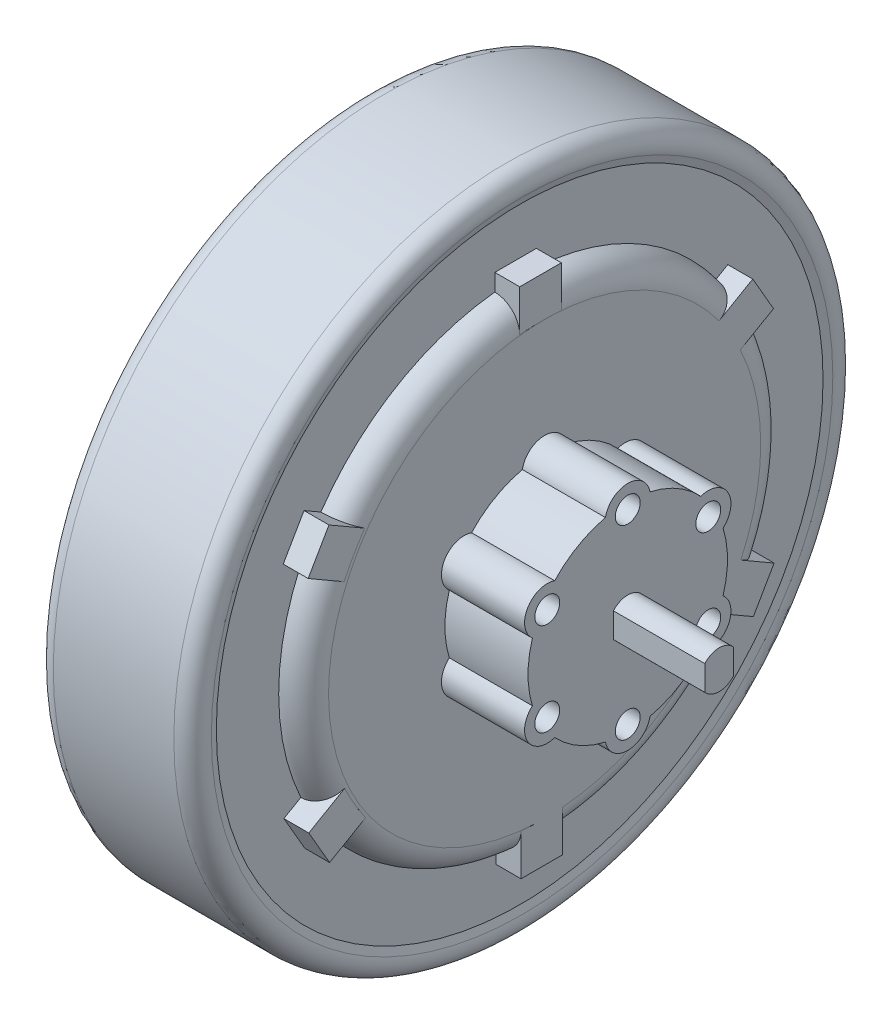
SolidWorks part; units mm, degrees
ref_plane "Front Plane" through (0, 0, 0) normal (0, 0, 1) x (1, 0, 0)
ref_plane "Top Plane" through (0, 0, 0) normal (0, 1, 0) x (1, 0, 0)
ref_plane "Right Plane" through (0, 0, 0) normal (1, 0, 0) x (0, 0, -1)
sketch "Sketch1" plane through (0, 0, 0) normal (0, 1, 0) x (1, 0, 0)
  line L0 (0, 0) -> (0, 89.9577) construction
  line L1 (-25.4, 89.9577) -> (25.4, 89.9577)
  line L2 (25.4, 89.9577) -> (22.528, 81.0677)
  line L3 (22.528, 81.0677) -> (22.528, 62.0177)
  line L4 (22.528, 62.0177) -> (30.148, 62.0177)
  line L5 (30.148, 62.0177) -> (30.148, 18.8377)
  line L6 (27.9161, -11.6423) -> (-27.9161, -11.6423)
  line L7 (0, -11.6423) -> (0, 89.9577)
  line L8 (30.148, 62.0177) -> (30.148, 68.7262) construction
  line L9 (30.148, 18.8377) -> (55.548, 18.8377)
  line L10 (55.548, 18.8377) -> (55.548, -11.6423)
  line L11 (55.548, -11.6423) -> (27.9161, -11.6423)
  line L12 (-30.148, 62.0177) -> (-30.148, 68.7262) construction
  line L13 (-30.148, -11.6423) -> (-27.9161, -11.6423)
  line L16 (-30.148, 62.0177) -> (-30.148, 18.8377)
  line L17 (-22.528, 62.0177) -> (-30.148, 62.0177)
  line L18 (-22.528, 81.0677) -> (-22.528, 62.0177)
  line L19 (-25.4, 89.9577) -> (-22.528, 81.0677)
  line L21 (-30.1884, -2.7523) -> (-36.5384, -2.7523)
  line L22 (-36.5384, -2.7523) -> (-36.5384, -4.5696)
  line L23 (-36.5384, -11.6423) -> (-30.148, -11.6423)
  line L24 (-30.1884, -2.7523) -> (-30.148, 18.8377)
  line L25 (-36.5384, -4.5696) -> (-38.4853, -4.5696)
  line L26 (-38.4853, -4.5696) -> (-38.4853, -11.6423)
  line L27 (-38.4853, -11.6423) -> (-36.5384, -11.6423)
  dimension "D1" = 101.6
  dimension "D2" = 8.89
  dimension "D3" = 19.05
  dimension "D4" = 7.62
  dimension "D5" = 90
  dimension "D6" = 25.4
  dimension "D7" = 6.35
  dimension "D8" = 25.4
  dimension "D9" = 71.12
  dimension "D10" = 8.89
revolve "Revolve1" add sketch "Sketch1" angle 360 about L6
ref_plane "Plane1" through (55.548, 0, 0) normal (1, 0, 0) x (0, 0, -1)
fillet "Fillet1" radius 7.62 2 edges at (30.148, 0, -62.0177) (-30.148, 0, -62.0177)
ref_plane "Plane2" through (-30.148, 0, 0) normal (-1, 0, 0) x (0, 0, 1)
sketch "Sketch3" plane through (-30.148, 0, 0) normal (-1, 0, 0) x (0, 0, 1)
  line L0 (6.5481, 65.8481) -> (6.5481, 78.4819)
  line L1 (6.5481, 78.4819) -> (19.2481, 78.4819)
  line L2 (19.2481, 78.4819) -> (19.2481, 65.7819)
  line L3 (12.8981, 30.4541) -> (12.8981, 78.4819) construction
  line L4 (83.9057, 33.5987) -> (72.9072, 27.2487)
  line L5 (77.5557, 44.5973) -> (83.9057, 33.5987)
  line L6 (66.6145, 38.2803) -> (77.5557, 44.5973)
  line L7 (77.3646, -44.838) -> (66.366, -38.488)
  line L8 (83.7146, -33.8395) -> (77.3646, -44.838)
  line L9 (72.7734, -27.5226) -> (83.7146, -33.8395)
  line L10 (6.1658, -78.3916) -> (6.1658, -65.6916)
  line L11 (18.8658, -78.3916) -> (6.1658, -78.3916)
  line L12 (18.8658, -65.7578) -> (18.8658, -78.3916)
  line L13 (-58.4919, -33.5084) -> (-47.4933, -27.1584)
  line L14 (-52.1419, -44.5069) -> (-58.4919, -33.5084)
  line L15 (-41.2006, -38.19) -> (-52.1419, -44.5069)
  line L16 (-51.9507, 44.9283) -> (-40.9522, 38.5783)
  line L17 (-58.3007, 33.9298) -> (-51.9507, 44.9283)
  line L18 (-47.3595, 27.6129) -> (-58.3007, 33.9298)
  circle A0 centre (11.6423, 0) radius 66.04 construction
  circle A1 centre (11.6423, 0) radius 30.48 construction
  circle A2 centre (11.6423, 0) radius 30.48 construction
  arc A3 (6.5481, 65.8481) -> (19.2481, 65.7819) centre (12.5157, -7.5698) cw
  arc A4 (66.6145, 38.2803) -> (72.9072, 27.2487) centre (6.0166, -3.5967) cw
  arc A5 (72.7734, -27.5226) -> (66.366, -38.488) centre (6.2078, 4.0183) cw
  arc A6 (18.8658, -65.7578) -> (6.1658, -65.6916) centre (12.8982, 7.6601) cw
  arc A7 (-41.2006, -38.19) -> (-47.4933, -27.1584) centre (19.3973, 3.687) cw
  arc A8 (-47.3595, 27.6129) -> (-40.9522, 38.5783) centre (19.206, -3.9279) cw
  point P41 (12.7069, 0.0452)
  dimension "D1" = 12.7
  dimension "D2" = 12.7
  dimension "D3" = 6
extrude "Boss-Extrude1" add sketch "Sketch3" against normal up to next
ref_plane "Plane3" through (0, 10.8699, 6.2757) normal (0, 0.866, 0.5) x (1, 0, 0)
sketch "Sketch5" plane through (0, 10.8699, 6.2757) normal (0, 0.866, 0.5) x (1, 0, 0)
  line L0 (-55.548, -10.0826) -> (-84.4313, -10.0826) construction
  line L1 (-55.548, 20.3974) -> (-55.548, -40.5626) construction
  line L2 (-30.4898, -79.7792) -> (-23.3898, -90.3477)
  line L5 (-23.3898, -90.3477) -> (-30.4898, -90.3477)
  line L6 (-30.4898, -90.3477) -> (-30.4898, -79.7792)
mirror "Mirror1" about plane through (0, 0, 0) normal (1, 0, 0) of "Boss-Extrude1"
sketch "Sketch7" plane through (55.548, 0, 0) normal (1, 0, 0) x (0, 0, -1)
  arc A0 (-18.451, 29.7098) -> (-4.8337, 29.7098) centre (-11.6423, 28.4042) cw
  circle A1 centre (-11.6423, 0) radius 30.48 construction
  arc A2 (-18.451, 29.7098) -> (-4.8337, 29.7098) centre (-11.6423, 0) cw
  arc A3 (10.6828, 20.7514) -> (17.4914, 8.9584) centre (-11.6423, 0) cw
  arc A4 (10.6828, 20.7514) -> (17.4914, 8.9584) centre (12.9564, 14.2021) cw
  arc A5 (17.4914, -8.9584) -> (10.6828, -20.7514) centre (-11.6423, 0) cw
  arc A6 (17.4914, -8.9584) -> (10.6828, -20.7514) centre (12.9564, -14.2021) cw
  arc A7 (-4.8337, -29.7098) -> (-18.451, -29.7098) centre (-11.6423, 0) cw
  arc A8 (-4.8337, -29.7098) -> (-18.451, -29.7098) centre (-11.6423, -28.4042) cw
  arc A9 (-33.9675, -20.7514) -> (-40.7761, -8.9584) centre (-11.6423, 0) cw
  arc A10 (-33.9675, -20.7514) -> (-40.7761, -8.9584) centre (-36.2411, -14.2021) cw
  arc A11 (-40.7761, 8.9584) -> (-33.9675, 20.7514) centre (-11.6423, 0) cw
  arc A12 (-40.7761, 8.9584) -> (-33.9675, 20.7514) centre (-36.2411, 14.2021) cw
  point P24 (-11.6423, 0)
  dimension "D1" = 6
extrude "Boss-Extrude2" add sketch "Sketch7" against normal up to next
sketch "Sketch8" plane through (55.548, 0, 0) normal (1, 0, 0) x (0, 0, -1)
  circle A0 centre (-11.6423, 28.4042) radius 3.81
  circle A1 centre (12.9564, 14.2021) radius 3.81
  circle A2 centre (12.9564, -14.2021) radius 3.81
  circle A3 centre (-11.6423, -28.4042) radius 3.81
  circle A4 centre (-36.2411, -14.2021) radius 3.81
  circle A5 centre (-36.2411, 14.2021) radius 3.81
  point P16 (-11.6423, 0)
  dimension "D1" = 6
extrude "Cut-Extrude1" cut sketch "Sketch8" against normal blind 10.16
sketch "Sketch9" plane through (55.548, 0, 0) normal (1, 0, 0) x (0, 0, -1)
  line L0 (-7.2635, 3.8093) -> (-7.2635, -3.8093)
  line L1 (-11.6423, 0) -> (-11.6423, 3.5304) construction
  line L2 (-16.0212, 3.8093) -> (-16.0212, -3.8093)
  arc A0 (-16.0212, -3.8093) -> (-7.2635, -3.8093) centre (-11.6423, 0) ccw
  arc A1 (-7.2635, 3.8093) -> (-16.0212, 3.8093) centre (-11.6423, 0) ccw
  dimension "D1" = 11.6078
extrude "Boss-Extrude3" add sketch "Sketch9" along normal blind 58.42 from offset 30.48 offset against normal yes
mirror "Mirror3" about plane through (0, 0, 0) normal (1, 0, 0) of "Boss-Extrude3"
fillet "Fillet2" radius 5.08 2 edges at (-25.4, 0, -89.9577) (25.4, 0, -89.9577)
sketch "Sketch10" plane through (0, 0, 0) normal (0, 0, 1) x (1, 0, 0)
  line L1 (-86.9993, 14.1566) -> (-59.5673, 14.1566)
  line L2 (-86.9993, 14.1566) -> (-86.9993, -9.7028)
  line L3 (-86.9993, -9.7028) -> (-59.5673, -9.7028)
  line L4 (-59.5673, 14.1566) -> (-59.5673, -9.7028)
  line L5 (-86.9993, 14.1566) -> (-59.5673, -9.7028) construction
  line L6 (-86.9993, -9.7028) -> (-59.5673, 14.1566) construction
  point P4 (-73.2833, 2.2269)
  dimension "D1" = 27.432
extrude "Cut-Extrude2" cut sketch "Sketch10" against normal through all both and the other way through all
